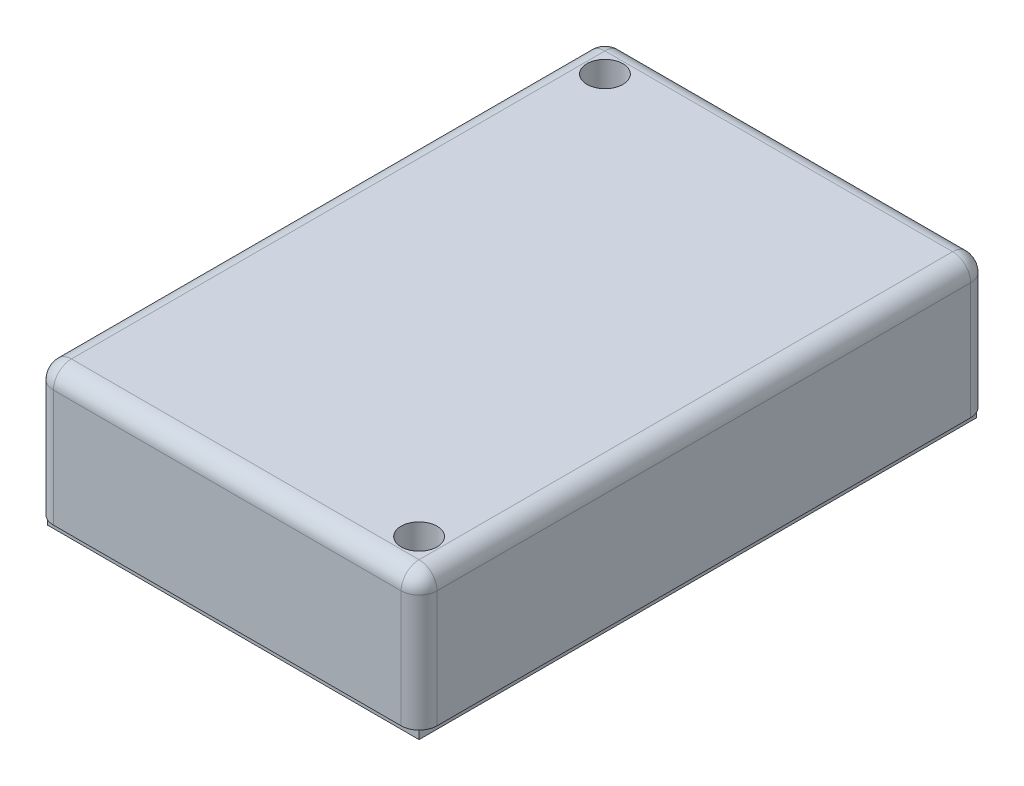
SolidWorks part; units mm, degrees
ref_plane "Front Plane" through (0, 0, 0) normal (0, 0, 1) x (1, 0, 0)
ref_plane "Top Plane" through (0, 0, 0) normal (0, 1, 0) x (1, 0, 0)
ref_plane "Right Plane" through (0, 0, 0) normal (1, 0, 0) x (0, 0, -1)
sketch "Sketch1" plane through (0, 0, 0) normal (0, 1, 0) x (1, 0, 0)
  line L5 (-32, -47.5) -> (32, -47.5)
  line L6 (-32, -47.5) -> (-32, 47.5)
  line L7 (-32, 47.5) -> (32, 47.5)
  line L8 (32, -47.5) -> (32, 47.5)
  line L9 (-32, -47.5) -> (32, 47.5) construction
  line L10 (-32, 47.5) -> (32, -47.5) construction
  point P0 (0, 0)
  dimension "D1" = 64
  dimension "D2" = 95
extrude "Boss-Extrude1" add sketch "Sketch1" along normal blind 2
sketch3d "3DSketch3"
  line L0 (-30, 0, 45.5) -> (-30, 0, -45.5)
  line L1 (-30, 0, -45.5) -> (30, 0, -45.5)
  line L2 (30, 0, -45.5) -> (30, 0, 45.5)
  line L3 (30, 0, 45.5) -> (-30, 0, 45.5)
  line L4 (-30, 0, 45.5) -> (-30, 0, -45.5)
  line L5 (-30, 0, -45.5) -> (30, 0, -45.5)
  line L6 (30, 0, -45.5) -> (30, 0, 45.5)
  line L7 (30, 0, 45.5) -> (-30, 0, 45.5)
  line L9 (-32, 0, 47.5) -> (-32, 0, -47.5)
  line L10 (-32, 0, 47.5) -> (32, 0, 47.5)
  line L11 (32, 0, 47.5) -> (32, 0, -47.5)
  line L12 (-32, 0, -47.5) -> (32, 0, -47.5)
  dimension "D1" = 2
extrude "Boss-Extrude2" add sketch "3DSketch3" along direction (0, -1, 0) on the side against the normal blind 22 contours L10 L9 L12 L11 | L4 L5 L6 L7
sketch3d "3DSketch4"
  line L0 (-31, -22, 46.5) -> (-31, -22, -46.5)
  line L1 (-32, -22, 47.5) -> (32, -22, 47.5)
  line L2 (-32, -22, 47.5) -> (-32, -22, -47.5)
  line L3 (-32, -22, -47.5) -> (32, -22, -47.5)
  line L4 (32, -22, 47.5) -> (32, -22, -47.5)
  line L5 (-31, -22, -46.5) -> (31, -22, -46.5)
  line L6 (31, -22, -46.5) -> (31, -22, 46.5)
  line L7 (31, -22, 46.5) -> (-31, -22, 46.5)
  line L8 (-31, -22, 46.5) -> (-31, -22, -46.5)
  line L9 (-31, -22, -46.5) -> (31, -22, -46.5)
  line L10 (31, -22, -46.5) -> (31, -22, 46.5)
  line L11 (31, -22, 46.5) -> (-31, -22, 46.5)
  dimension "D1" = 1
extrude "Cut-Extrude5" cut sketch "3DSketch4" along a picked direction on the side of the normal blind 1.5
fillet "Fillet1" radius 10 4 edges
sketch "Sketch3" plane through (0, 0, -47.5) normal (0, 0, -1) x (-1, 0, 0)
  line L0 (32, -20.5) -> (-32, -20.5) construction
  circle A0 centre (0, -20.5) radius 4
extrude "Cut-Extrude6" cut sketch "Sketch3" against normal up to next
sketch "Sketch4" plane through (0, 0, 0) normal (0, -1, 0) x (-1, 0, 0)
  line L0 (12.75, 37.0679) -> (12.75, 40.5679)
  line L5 (12.75, 40.5679) -> (-22.75, 40.5679)
  line L6 (-22.75, 37.0679) -> (-22.75, 40.5679)
  line L7 (12.75, 37.0679) -> (-22.75, 37.0679)
  line L8 (15.25, 34.5679) -> (-25.25, 34.5679)
  line L9 (-25.25, 34.5679) -> (-25.25, 43.0679)
  line L10 (15.25, 43.0679) -> (-25.25, 43.0679)
  line L11 (15.25, 34.5679) -> (15.25, 43.0679)
  dimension "D2" = 2.5
extrude "Boss-Extrude3" add sketch "Sketch4" along normal blind 20.5
sketch "Sketch5" plane through (0, 0, 0) normal (0, -1, 0) x (-1, 0, 0)
  line L1 (12.75, 37.0679) -> (-22.75, 37.0679)
  line L2 (12.75, 37.0679) -> (12.75, 40.5679)
  line L3 (12.75, 40.5679) -> (-22.75, 40.5679)
  line L4 (-22.75, 37.0679) -> (-22.75, 40.5679)
extrude "Boss-Extrude4" add sketch "Sketch5" along normal blind 11.4
sketch "Sketch6" plane through (0, 0, -34.5679) normal (0, 0, 1) x (1, 0, 0)
  line L0 (25.25, -20.5) -> (-15.25, -20.5) construction
  line L1 (15.25, -20.5) -> (-4.75, -20.5)
  line L2 (15.25, -20.5) -> (15.25, -16)
  line L3 (15.25, -16) -> (-4.75, -16)
  line L4 (-4.75, -20.5) -> (-4.75, -16)
  line L6 (-15.25, -20.5) -> (-15.25, 0) construction
  dimension "D1" = 10.5
  dimension "D2" = 20
  dimension "D3" = 4.5
extrude "Cut-Extrude7" cut sketch "Sketch6" against normal up to surface (8.5 mm away) up to face at (5, -10.25, -43.0679)
chamfer "Chamfer2" distance 4.2 angle 45 1 edges at (15.25, -20.5, -35.8179)
sketch "Sketch8" plane through (0, 2, 0) normal (0, 1, 0) x (1, 0, 0)
  line L5 (31, -46.5) -> (16, -31.5) construction
  line L10 (-31, 46.5) -> (-16, 31.5) construction
  circle A0 centre (-25.6575, 41.1575) radius 3
  circle A1 centre (-25.6575, 41.1575) radius 5
  circle A4 centre (25.6575, -41.1575) radius 5
  circle A5 centre (25.6575, -41.1575) radius 3
  point P0 (0, 0)
  dimension "D3" = 21.9203
  dimension "D1" = 48.5
  dimension "D2" = 48.5
extrude "Boss-Extrude6" add sketch "Sketch8" against normal up to surface (24 mm away) up to face at (0.4635, -22, -11.5)
sketch "Sketch9" plane through (0, -22, 0) normal (0, -1, 0) x (1, 0, 0)
sketch "Sketch10" plane through (0, -22, 0) normal (0, -1, 0) x (1, 0, 0)
  circle A0 centre (-25.6575, -41.1575) radius 3
  circle A1 centre (25.6575, 41.1575) radius 3
extrude "Cut-Extrude9" cut sketch "Sketch10" against normal up to surface (24 mm away) up to face at (0, 2, 0)
sketch "Sketch11" plane through (0, -22, 0) normal (0, -1, 0) x (1, 0, 0)
  circle A0 centre (25.6575, 41.1575) radius 3
  circle A1 centre (-25.6575, -41.1575) radius 3
extrude "Boss-Extrude7" add sketch "Sketch11" against normal blind 4
sketch "Sketch12" plane through (0, -22, 0) normal (0, -1, 0) x (1, 0, 0)
  circle A0 centre (25.6575, 41.1575) radius 1.25
  circle A1 centre (-25.6575, -41.1575) radius 1.25
extrude "Cut-Extrude10" cut sketch "Sketch12" against normal blind 4
fillet "Fillet2" radius 3 4 edges
fillet "Fillet3" radius 3 8 edges at (-32, 2, 0) (-31.1213, 2, -46.6213) (0, 2, -47.5) (31.1213, 2, -46.6213) (32, 2, 0) (31.1213, 2, 46.6213) (0, 2, 47.5) (-31.1213, 2, 46.6213)
sketch "Sketch13" plane through (0, 0, 0) normal (0, -1, 0) x (1, 0, 0)
  line L0 (15.25, -43.0679) -> (25.25, -43.0679) construction
  line L1 (20.25, -43.0679) -> (17.25, -43.0679)
  line L2 (20.25, -43.0679) -> (20.25, -45.5)
  line L3 (20.25, -45.5) -> (17.25, -45.5)
  line L4 (17.25, -43.0679) -> (17.25, -45.5)
  line L5 (-20, -45.5) -> (20, -45.5) construction
  line L6 (-20, -45.5) -> (-3.7081, -45.5) construction
  line L7 (-9.6939, -45.5) -> (-12.6939, -45.5)
  line L8 (-9.6939, -45.5) -> (-9.6939, -43.0679)
  line L9 (-9.6939, -43.0679) -> (-12.6939, -43.0679)
  line L10 (-12.6939, -45.5) -> (-12.6939, -43.0679)
  line L11 (-15.25, -43.0679) -> (-4.75, -43.0679) construction
  dimension "D1" = 3
  dimension "D2" = 3
extrude "Boss-Extrude8" add sketch "Sketch13" along normal up to surface (20.5 mm away) up to face at (-9.375, -20.5, -38.8179)
fillet "Fillet4" radius 1 4 edges at (-12.6939, -10.25, -45.5) (17.25, -10.25, -45.5) (20.25, -10.25, -45.4969) (-9.6939, -10.25, -45.5)
fillet "Fillet5" radius 2 3 edges at (-15.25, 0, -38.8179) (5, 0, -34.5679) (25.25, 0, -38.8179)
chamfer "Chamfer3" distance 1.7 angle 45 1 edges at (-25.6575, -18, -44.1575)
chamfer "Chamfer4" distance 1.7 angle 45 1 edges at (25.6575, -18, 38.1575)
